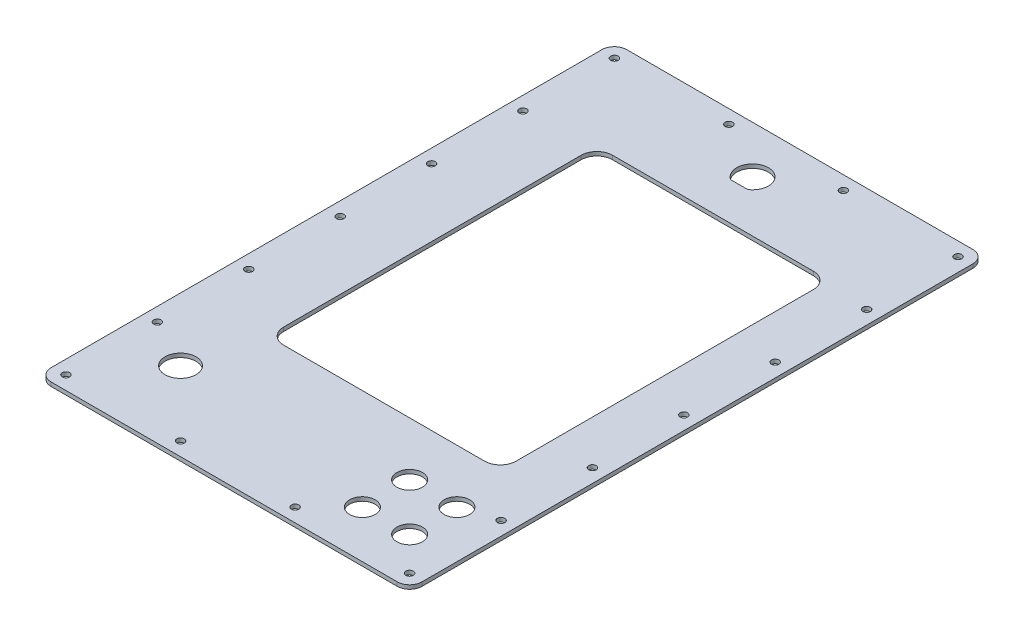
SolidWorks part; units mm, degrees
material "5052-H32"
ref_plane "Front Plane" through (0, 0, 0) normal (0, 0, 1) x (1, 0, 0)
ref_plane "Top Plane" through (0, 0, 0) normal (0, 1, 0) x (1, 0, 0)
ref_plane "Right Plane" through (0, 0, 0) normal (1, 0, 0) x (0, 0, -1)
sketch "Sketch9" plane through (0, 0, 0) normal (0, 1, 0) x (1, 0, 0)
  line L0 (-149.5, 0) -> (-149.5, 464)
  line L13 (-149.5, 464) -> (149.5, 464)
  line L14 (103.1625, 119.4438) -> (-84.1625, 119.4438)
  line L19 (149.5, 464) -> (149.5, 0)
  line L20 (103.1625, 119.4438) -> (103.1625, 384.5563)
  line L21 (103.1625, 384.5563) -> (-84.1625, 384.5563)
  line L22 (-84.1625, 119.4438) -> (-84.1625, 384.5563)
  line L23 (103.1625, 252) -> (-84.1625, 252) construction
  line L24 (9.5, 384.5562) -> (9.5, 119.4438) construction
  line L25 (-149.5, 0) -> (149.5, 0)
  line L26 (0, 464) -> (0, 425.9) construction
  line L27 (6.8702, 415.1) -> (-6.8702, 415.1)
  arc A0 (6.8702, 415.1) -> (-6.8702, 415.1) centre (0, 425.9) ccw
  circle A1 centre (-98.7, 63.5) radius 12.5
  circle A2 centre (111.4, 76.2) radius 10.287
  circle A3 centre (111.4, 38.1) radius 10.287
  circle A4 centre (73.3, 76.2) radius 10.287
  circle A5 centre (73.3, 38.1) radius 10.287
  point P8 (0, 0)
  point P17 (0, 438.7)
  point P19 (0, 0)
  dimension "D8" = 25.6
  dimension "D10" = 25
  dimension "D3" = 265.1125
  dimension "D4" = 187.325
  dimension "D1" = 299
  dimension "D2" = 464
  dimension "D6" = 140
  dimension "D5" = 212
  dimension "D7" = 23.6
  dimension "D12" = 38.1
  dimension "D13" = 38.1
  dimension "D15" = 38.1
  dimension "D16" = 63.5
  dimension "D17" = 50.8
  dimension "D14" = 38.1
  dimension "D9" = 38.1
extrude "Boss-Extrude7" add sketch "Sketch9" along normal blind 3.175 separate body contours L0 L25 L19 L13 L14 L22 L21 L20 region at (-143.9801, 0, -232)
fillet "Fillet4" radius 10 4 edges at (-149.5, 1.5875, -464) (149.5, 1.5875, -464) (-149.5, 1.5875, 0) (149.5, 1.5875, 0)
fillet "Fillet5" radius 12.7 4 edges at (-84.1625, 1.5875, -119.4438) (103.1625, 1.5875, -119.4438) (103.1625, 1.5875, -384.5563) (-84.1625, 1.5875, -384.5563)
sketch "Sketch10" plane through (0, 3.175, 0) normal (0, 1, 0) x (1, 0, 0)
  line L0 (-149.5, 10) -> (-149.5, 454) construction
  line L1 (-139.5, 0) -> (139.5, 0) construction
  circle A0 centre (-138.5, 11) radius 3
  circle A1 centre (-46.1667, 11) radius 3
  circle A2 centre (46.1667, 11) radius 3
  circle A3 centre (138.5, 11) radius 3
  circle A56 centre (-138.5, 84.6667) radius 3
  circle A57 centre (-138.5, 158.3333) radius 3
  circle A58 centre (-138.5, 232) radius 3
  circle A59 centre (-138.5, 305.6667) radius 3
  circle A60 centre (-138.5, 379.3333) radius 3
  circle A61 centre (-138.5, 453) radius 3
  circle A68 centre (138.5, 84.6667) radius 3
  circle A72 centre (138.5, 158.3333) radius 3
  circle A76 centre (138.5, 232) radius 3
  circle A80 centre (138.5, 305.6667) radius 3
  circle A84 centre (138.5, 379.3333) radius 3
  circle A86 centre (-46.1667, 453) radius 3
  circle A87 centre (46.1667, 453) radius 3
  circle A88 centre (138.5, 453) radius 3
  circle A102 centre (-46.1667, 84.6667) radius 3 [skipped]
  circle A103 centre (46.1667, 84.6667) radius 3 [skipped]
  circle A104 centre (-46.1667, 158.3333) radius 3 [skipped]
  circle A105 centre (46.1667, 158.3333) radius 3 [skipped]
  circle A106 centre (-46.1667, 232) radius 3 [skipped]
  circle A107 centre (46.1667, 232) radius 3 [skipped]
  circle A108 centre (-46.1667, 305.6667) radius 3 [skipped]
  circle A109 centre (46.1667, 305.6667) radius 3 [skipped]
  circle A110 centre (-46.1667, 379.3333) radius 3 [skipped]
  circle A111 centre (46.1667, 379.3333) radius 3 [skipped]
  dimension "D2" = 11
  dimension "D3" = 11
  dimension "D6" = 73.6667
  dimension "D7" = 92.3333
  dimension "D4" = 4
  dimension "D5" = 7
extrude "Cut-Extrude1" cut sketch "Sketch10" against normal up to surface (3.175 mm away) up to face at (73.3, 0, -27.813)
equation "\"W\"= 255mm"
equation "\"L\"= 420mm"
equation "\"Offset\"= 18mm"
equation "\"H\"= 110mm"
equation "\"T\"= 4.7625 * 2 / 3mm"
equation "\"Inside Fillet Radius\"= 5.55625mm"
equation "\"Hole\"=25mm"
equation "\"D1@Sketch9\"=\"W\"+44"
equation "\"D2@Sketch9\"=\"L\"+44"
equation "\"D6@Sketch10\"=(\"L\"+22)/6"
equation "\"D7@Sketch10\"=(\"W\"+22)/3"
equation "\"D5@Sketch9\"=(\"L\"/2+20)-\"Offset\""
equation "\"Compartment Width1\"= 90mm"
equation "\"Compartment Width2\"= 90mm"
